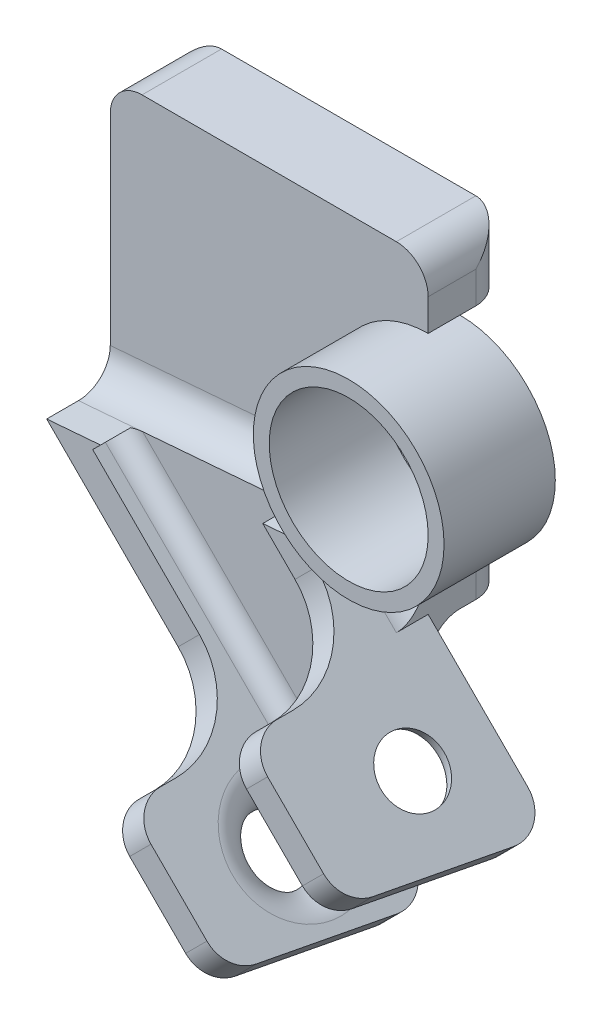
SolidWorks part; units mm, degrees
ref_plane "Alzado" through (0, 0, 0) normal (0, 0, 1) x (1, 0, 0)
ref_plane "Planta" through (0, 0, 0) normal (0, 1, 0) x (1, 0, 0)
ref_plane "Vista lateral" through (0, 0, 0) normal (1, 0, 0) x (0, 0, -1)
sketch "Croquis1" plane through (0, 0, 0) normal (0, 0, 1) x (1, 0, 0)
  circle A0 centre (0, 0) radius 6
  circle A1 centre (0, 0) radius 5
  dimension "D1" = 12
  dimension "D2" = 10
extrude "Saliente-Extruir1" add sketch "Croquis1" along normal blind 7
sketch "Croquis2" plane through (0, 0, 0) normal (0, 0, -1) x (-1, 0, 0)
  line L0 (0, -10) -> (0, -5)
  line L1 (0, -10) -> (20, -10)
  line L2 (0, 10) -> (20, 10)
  line L3 (20, -10) -> (20, 10)
  line L4 (0, 5) -> (0, 10)
  line L5 (0, 0) -> (20, 0) construction
  line L6 (0, 0) -> (0, 5.568) construction
  circle A1 centre (0, 0) radius 5 construction
  arc A2 (0, -5) -> (0, 5) centre (0, 0) ccw
  dimension "D1" = 20
  dimension "D2" = 20
  dimension "D3" = 10
extrude "Saliente-Extruir2" add sketch "Croquis2" against normal blind 2 and the other way blind 3
sketch "Croquis4" plane through (0, 0, -3) normal (0, 0, -1) x (-1, 0, 0)
  line L0 (20, -10) -> (20, 10) construction
  line L1 (20, -8.25) -> (0, -8.25)
  line L2 (20, -8.25) -> (20, 8.25)
  line L3 (20, 8.25) -> (0, 8.25)
  line L4 (0, -8.25) -> (0, 8.25)
  line L5 (0, 10) -> (0, 5) construction
  line L6 (20, 10) -> (0, 10) construction
  dimension "D1" = 16.5
  dimension "D2" = 1.75
extrude "Cortar-Extruir1" cut sketch "Croquis4" against normal blind 4
sketch "Croquis5" plane through (0, 0, 2) normal (0, 0, 1) x (1, 0, 0)
  line L0 (-3.9474, -5.3578) -> (-20, -6.6592)
  line L1 (-3.9474, -5.3578) -> (16.7598, -26.065)
  line L2 (-20, -6.6592) -> (0.7072, -27.3664)
  line L3 (16.7598, -26.065) -> (0.7072, -27.3664)
  line L4 (-20, 10) -> (0, 10) construction
  line L6 (-20, -10) -> (-20, 10) construction
  dimension "D1" = 45
extrude "Saliente-Extruir7" add sketch "Croquis5" along normal blind 4
sketch "Croquis10" plane through (0, 0, 6) normal (0, 0, 1) x (1, 0, 0)
  line L0 (-0.7652, -25.894) -> (7.9118, -17.217)
  line L1 (-20, -6.6592) -> (0.7072, -27.3664) construction
  line L2 (16.7598, -26.065) -> (-3.9474, -5.3578) construction
  line L3 (7.9118, -17.217) -> (16.7598, -26.065)
  line L4 (16.7598, -26.065) -> (0.7072, -27.3664)
  line L5 (0.7072, -27.3664) -> (-0.7652, -25.894)
extrude "Cortar-Extruir4" cut sketch "Croquis10" against normal up to surface (4 mm away) up to face at (0.1616, -16.5473, 2)
sketch "Croquis11" plane through (0, 0, 6) normal (0, 0, 1) x (1, 0, 0)
  line L0 (0.5721, -24.5568) -> (6.5825, -18.5464)
  line L1 (7.9118, -17.217) -> (-0.7652, -25.894) construction
  line L2 (6.5825, -18.5464) -> (-0.8421, -11.1217)
  line L3 (-0.8421, -11.1217) -> (-6.8526, -17.1321)
  line L4 (-6.8526, -17.1321) -> (0.5721, -24.5568)
  line L5 (7.9118, -17.217) -> (-3.9474, -5.3578) construction
  dimension "D1" = 8.5
  dimension "D2" = 10.5
  dimension "D3" = 1.88
extrude "Cortar-Extruir5" cut sketch "Croquis11" against normal blind 2.2
sketch "Croquis12" plane through (0, 0, 6) normal (0, 0, 1) x (1, 0, 0)
  line L0 (-6.8526, -17.1321) -> (-8.1898, -18.4694)
  line L1 (-20, -6.6592) -> (-0.7652, -25.894) construction
  line L2 (-8.1898, -18.4694) -> (-0.7652, -25.894)
  line L3 (-0.7652, -25.894) -> (0.5721, -24.5568)
  line L4 (0.5721, -24.5568) -> (-6.8526, -17.1321)
  line L5 (-0.8421, -11.1217) -> (0.4872, -9.7924)
  line L6 (7.9118, -17.217) -> (-3.9474, -5.3578) construction
  line L7 (0.4872, -9.7924) -> (7.9118, -17.217)
  line L8 (7.9118, -17.217) -> (6.5825, -18.5464)
  line L9 (6.5825, -18.5464) -> (-0.8421, -11.1217)
extrude "Saliente-Extruir9" add sketch "Croquis12" along normal blind 8
sketch "Croquis13" plane through (-13.3296, -13.3296, 0) normal (-0.7071, -0.7071, 0) x (0, 0, 1)
  line L0 (2, 4.7088) -> (2, -17.7688) construction
  line L1 (2, -17.7688) -> (14, -17.7688) construction
  circle A0 centre (7, -12.2688) radius 2
  dimension "D3" = 4
  dimension "D1" = 5
  dimension "D2" = 5.5
extrude "Cortar-Extruir6" cut sketch "Croquis13" against normal up to surface (12.2712 mm away) up to face at (1.2719, -10.5771, 6.5714)
fillet "Redondeo1" radius 2 2 edges at (-1.9028, -22.0819, 7) (1.2792, -13.243, 7)
sketch "Croquis14" plane through (12.5644, -12.5644, 0) normal (0.7071, -0.7071, 0) x (0, 0, -1)
  line L5 (-2, -6.5797) -> (-2, -18.8509) construction
  line L10 (-3.8, -8.4597) -> (-2, -8.4597)
  line L11 (-3.8, -8.4597) -> (-3.8, -16.9597)
  line L12 (-3.8, -16.9597) -> (-2, -16.9597)
  line L13 (-2, -8.4597) -> (-2, -16.9597)
extrude "Cortar-Extruir7" cut sketch "Croquis14" against normal blind 10.5
sketch "Croquis15" plane through (5.1398, -5.1398, 0) normal (0.7071, -0.7071, 0) x (0, 0, -1)
  line L0 (-2, -8.4597) -> (-6, -8.4597) construction
  line L1 (-6, -16.9597) -> (-4, -16.9597)
  line L2 (-6, -16.9597) -> (-6, -8.4597)
  line L3 (-6, -8.4597) -> (-4, -8.4597)
  line L4 (-4, -16.9597) -> (-4, -8.4597)
extrude "Cortar-Extruir8" cut sketch "Croquis15" against normal blind 14.5
fillet "Redondeo2" radius 2 3 edges at (-1.9737, -7.3315, 2) (-11.9737, -6.0085, 2) (-8.3296, -10, 2)
fillet "Redondeo3" radius 2 1 edges at (-18.3296, -8.3296, 2)
fillet "Redondeo4" radius 5 2 edges at (-7.5212, -17.8008, 6) (-0.1775, -10.457, 6)
sketch "Croquis16" plane through (-13.3296, -13.3296, 0) normal (-0.7071, -0.7071, 0) x (0, 0, 1)
  line L0 (2, -17.7688) -> (14, -15.9688)
  line L1 (14, -7.2688) -> (14, -17.7688) construction
  line L2 (14, -15.9688) -> (14, -17.7688)
  line L3 (14, -17.7688) -> (2, -17.7688)
  dimension "D1" = 1.8
extrude "Cortar-Extruir9" cut sketch "Croquis16" against normal up to surface (12.2712 mm away) up to face at (5.437, -14.7421, 7)
fillet "Redondeo5" radius 2 6 edges at (7.2472, -17.8817, 2) (-0.0966, -25.2254, 2) (-0.1775, -10.457, 14) (-7.5212, -17.8008, 14) (-1.3694, -23.9526, 14) (5.9744, -16.6089, 14)
fillet "Redondeo6" radius 1.2 4 edges at (-6.8526, -17.1321, 3) (-0.8421, -11.1217, 2.8984) (-11.9791, -12.0056, 4) (-3.6244, -8.3395, 4)
sketch "Croquis20" plane through (0, 0, 1) normal (0, 0, -1) x (-1, 0, 0)
  line L7 (0, -8.25) -> (20, -8.25)
  line L8 (20, -8.25) -> (20, 8.25)
  line L9 (0, -8.25) -> (20, -8.25)
  line L10 (0, 8.25) -> (0, 6)
  line L11 (0, 6) -> (0, 5)
  line L12 (0, -5) -> (0, -6)
  line L13 (0, -6) -> (0, -8.25)
  line L15 (20, -8.25) -> (20, 8.25)
  line L17 (0, 8.25) -> (0, 6)
  line L18 (0, 6) -> (0, 5)
  line L19 (0, -5) -> (0, -6)
  line L20 (0, -6) -> (0, -8.25)
  line L21 (20, 8.25) -> (0, 8.25)
  line L22 (20, 8.25) -> (0, 8.25)
  arc A1 (0, -5) -> (0, 5) centre (0, 0) ccw
  arc A2 (0, -5) -> (0, 5) centre (0, 0) ccw
  dimension "D1" = 0
extrude "Saliente-Extruir12" add sketch "Croquis20" along normal up to surface (1 mm away) up to face at (2.75, 0, 0)
sketch "Croquis21" plane through (0, 0, 0) normal (0, 0, -1) x (-1, 0, 0)
  line L0 (20, -8.25) -> (20, -4.25)
  line L1 (20, 8.25) -> (20, -8.25) construction
  line L2 (20, -4.25) -> (0, -6)
  line L3 (0, -8.25) -> (0, -6) construction
  line L4 (0, -8.25) -> (20, -8.25)
  line L6 (0, 6) -> (20, 7.45)
  line L7 (20, 7.45) -> (20, 8.25)
  line L8 (20, 8.25) -> (0, 8.25)
  line L9 (0, 8.25) -> (0, 6)
  line M8 (0, -6) -> (0, -8.25)
  line M9 (0, -8.25) -> (20, -8.25)
  line M10 (20, -8.25) -> (20, 8.25)
  line M11 (20, 8.25) -> (0, 8.25)
  line M12 (0, 8.25) -> (0, 6)
  dimension "D1" = 0.8
  dimension "D2" = 4
extrude "Saliente-Extruir13" add sketch "Croquis21" along normal up to surface (3 mm away) contours L2 M10 M8 M9 | L6 M12 M10 M11 up to face at (-10, -9.125, -3)
fillet "Redondeo7" radius 2 7 edges at (-20, -10, -0.5) (-20, 10, -0.5) (-20, 8.725, -3) (-20, -7.125, -3) (0, -8, -3) (0, 8, -3) (0, 10, -0.5)
